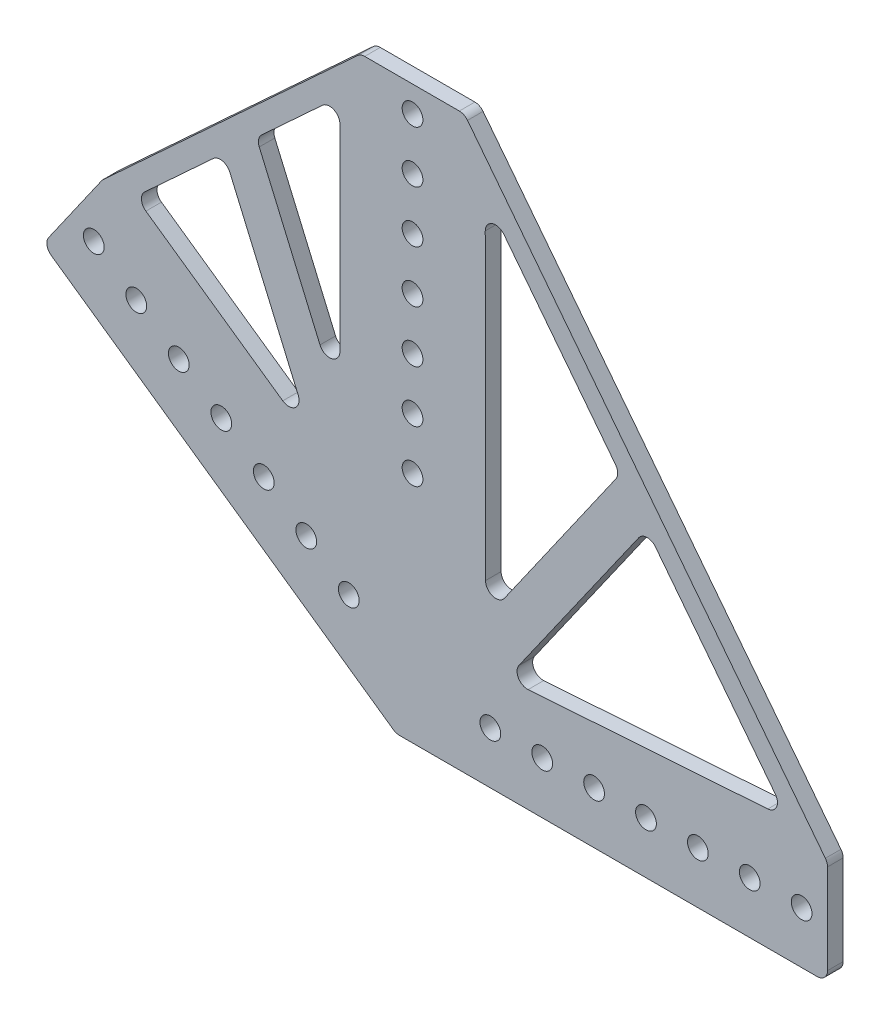
SolidWorks part; units mm, degrees
ref_plane "Front Plane" through (0, 0, 0) normal (0, 0, 1) x (1, 0, 0)
ref_plane "Top Plane" through (0, 0, 0) normal (0, 1, 0) x (1, 0, 0)
ref_plane "Right Plane" through (0, 0, 0) normal (1, 0, 0) x (0, 0, -1)
sketch "Sketch1" plane through (0, 0, 0) normal (0, 0, 1) x (1, 0, 0)
  line L0 (-280.0652, 184.4073) -> (-30.3877, 9.5812)
  line L1 (0, 0) -> (431.8, 0)
  line L2 (0, 0) -> (0, 25.4)
  line L3 (0, 25.4) -> (431.8, 25.4)
  line L4 (431.8, 0) -> (431.8, 25.4)
  line L5 (-280.0652, 184.4073) -> (-265.4964, 205.2137)
  line L6 (-30.3877, 9.5812) -> (-15.8188, 30.3877)
  line L7 (-265.4964, 205.2137) -> (-15.8188, 30.3877)
  line L8 (-25.4, 50.8) -> (0, 50.8)
  line L9 (-25.4, 50.8) -> (-25.4, 355.6)
  line L10 (0, 50.8) -> (0, 355.6)
  line L11 (-25.4, 355.6) -> (0, 355.6)
  line L12 (-225.8432, 161.9445) -> (23.8343, -12.8816) construction
  line L13 (0, 12.7) -> (431.8, 12.7) construction
  line L14 (-12.7, 12.7) -> (-12.7, 105.3379) construction
  line L15 (-12.7, 57.15) -> (-12.7, 69.85) construction
  line L16 (6.35, 12.7) -> (19.05, 12.7) construction
  line L17 (-28.3048, 23.6266) -> (-38.7081, 30.9111) construction
  line L18 (-103.2103, 60.5721) -> (-88.6414, 81.3786)
  line L20 (-25.4, 139.7) -> (0, 139.7)
  line L22 (88.9, 25.4) -> (88.9, 0)
  line L23 (88.9, 0) -> (-16.7043, 0)
  line L24 (-16.7043, 0) -> (-103.2103, 60.5721)
  line L25 (-88.6414, 81.3786) -> (-15.8188, 30.3877) construction
  line L26 (0, 25.4) -> (88.9, 25.4) construction
  line L27 (-25.4, 139.7) -> (-25.4, 50.8) construction
  line L28 (0, 139.7) -> (0, 50.8) construction
  line L29 (0, 0) -> (88.9, 0) construction
  line L30 (-88.6414, 81.3786) -> (-25.4, 139.7)
  line L31 (0, 139.7) -> (88.9, 25.4)
  circle A0 centre (-12.7, 57.15) radius 2.54
  circle A1 centre (-12.7, 69.85) radius 2.54
  circle A2 centre (-12.7, 82.55) radius 2.54
  circle A3 centre (-12.7, 95.25) radius 2.54
  circle A4 centre (-12.7, 107.95) radius 2.54
  circle A5 centre (-12.7, 120.65) radius 2.54
  circle A6 centre (-12.7, 133.35) radius 2.54
  circle A7 centre (-12.7, 146.05) radius 2.54
  circle A8 centre (-12.7, 158.75) radius 2.54
  circle A9 centre (-12.7, 171.45) radius 2.54
  circle A10 centre (-12.7, 184.15) radius 2.54
  circle A11 centre (-12.7, 196.85) radius 2.54
  circle A12 centre (-12.7, 209.55) radius 2.54
  circle A13 centre (-12.7, 222.25) radius 2.54
  circle A14 centre (-12.7, 234.95) radius 2.54
  circle A15 centre (-12.7, 247.65) radius 2.54
  circle A16 centre (-12.7, 260.35) radius 2.54
  circle A17 centre (-12.7, 273.05) radius 2.54
  circle A18 centre (-12.7, 285.75) radius 2.54
  circle A19 centre (-12.7, 298.45) radius 2.54
  circle A20 centre (-12.7, 311.15) radius 2.54
  circle A21 centre (-12.7, 323.85) radius 2.54
  circle A22 centre (-12.7, 336.55) radius 2.54
  circle A23 centre (-12.7, 349.25) radius 2.54
  circle A24 centre (6.35, 12.7) radius 2.54
  circle A25 centre (19.05, 12.7) radius 2.54
  circle A26 centre (31.75, 12.7) radius 2.54
  circle A27 centre (44.45, 12.7) radius 2.54
  circle A28 centre (57.15, 12.7) radius 2.54
  circle A29 centre (69.85, 12.7) radius 2.54
  circle A30 centre (82.55, 12.7) radius 2.54
  circle A31 centre (95.25, 12.7) radius 2.54
  circle A32 centre (107.95, 12.7) radius 2.54
  circle A33 centre (120.65, 12.7) radius 2.54
  circle A34 centre (133.35, 12.7) radius 2.54
  circle A35 centre (146.05, 12.7) radius 2.54
  circle A36 centre (158.75, 12.7) radius 2.54
  circle A37 centre (171.45, 12.7) radius 2.54
  circle A38 centre (184.15, 12.7) radius 2.54
  circle A39 centre (196.85, 12.7) radius 2.54
  circle A40 centre (209.55, 12.7) radius 2.54
  circle A41 centre (222.25, 12.7) radius 2.54
  circle A42 centre (234.95, 12.7) radius 2.54
  circle A43 centre (247.65, 12.7) radius 2.54
  circle A44 centre (260.35, 12.7) radius 2.54
  circle A45 centre (273.05, 12.7) radius 2.54
  circle A46 centre (285.75, 12.7) radius 2.54
  circle A47 centre (298.45, 12.7) radius 2.54
  circle A48 centre (311.15, 12.7) radius 2.54
  circle A49 centre (323.85, 12.7) radius 2.54
  circle A50 centre (336.55, 12.7) radius 2.54
  circle A51 centre (349.25, 12.7) radius 2.54
  circle A52 centre (361.95, 12.7) radius 2.54
  circle A53 centre (374.65, 12.7) radius 2.54
  circle A54 centre (387.35, 12.7) radius 2.54
  circle A55 centre (400.05, 12.7) radius 2.54
  circle A56 centre (412.75, 12.7) radius 2.54
  circle A57 centre (425.45, 12.7) radius 2.54
  circle A58 centre (-28.3048, 23.6266) radius 2.54
  circle A59 centre (-38.7081, 30.9111) radius 2.54
  circle A60 centre (-49.1113, 38.1955) radius 2.54
  circle A61 centre (-59.5145, 45.4799) radius 2.54
  circle A62 centre (-69.9178, 52.7643) radius 2.54
  circle A63 centre (-80.321, 60.0487) radius 2.54
  circle A64 centre (-90.7242, 67.3332) radius 2.54
  circle A65 centre (-101.1275, 74.6176) radius 2.54
  circle A66 centre (-111.5307, 81.902) radius 2.54
  circle A67 centre (-121.9339, 89.1864) radius 2.54
  circle A68 centre (-132.3372, 96.4708) radius 2.54
  circle A69 centre (-142.7404, 103.7553) radius 2.54
  circle A70 centre (-153.1436, 111.0397) radius 2.54
  circle A71 centre (-163.5468, 118.3241) radius 2.54
  circle A72 centre (-173.9501, 125.6085) radius 2.54
  circle A73 centre (-184.3533, 132.8929) radius 2.54
  circle A74 centre (-194.7565, 140.1774) radius 2.54
  circle A75 centre (-205.1598, 147.4618) radius 2.54
  circle A76 centre (-215.563, 154.7462) radius 2.54
  circle A77 centre (-225.9662, 162.0306) radius 2.54
  circle A78 centre (-236.3695, 169.315) radius 2.54
  circle A79 centre (-246.7727, 176.5995) radius 2.54
  circle A80 centre (-257.1759, 183.8839) radius 2.54
  circle A81 centre (-267.5792, 191.1683) radius 2.54
  circle A82 centre (-80.321, 60.0487) radius 2.54
  circle A83 centre (-69.9178, 52.7643) radius 2.54
  circle A84 centre (-59.5145, 45.4799) radius 2.54
  circle A85 centre (-49.1113, 38.1955) radius 2.54
  circle A86 centre (-38.7081, 30.9111) radius 2.54
  circle A87 centre (-28.3048, 23.6266) radius 2.54
  circle A88 centre (82.55, 12.7) radius 2.54
  circle A89 centre (-12.7, 133.35) radius 2.54
  circle A90 centre (-90.7242, 67.3332) radius 2.54
  circle A91 centre (69.85, 12.7) radius 2.54
  circle A92 centre (57.15, 12.7) radius 2.54
  circle A93 centre (44.45, 12.7) radius 2.54
  circle A94 centre (31.75, 12.7) radius 2.54
  circle A95 centre (19.05, 12.7) radius 2.54
  circle A96 centre (6.35, 12.7) radius 2.54
  circle A97 centre (-12.7, 120.65) radius 2.54
  circle A98 centre (-12.7, 107.95) radius 2.54
  circle A99 centre (-12.7, 95.25) radius 2.54
  circle A100 centre (-12.7, 82.55) radius 2.54
  circle A101 centre (-12.7, 69.85) radius 2.54
  circle A102 centre (-12.7, 57.15) radius 2.54
  circle A103 centre (-80.321, 60.0487) radius 2.54
  circle A104 centre (-69.9178, 52.7643) radius 2.54
  circle A105 centre (-59.5145, 45.4799) radius 2.54
  circle A106 centre (-49.1113, 38.1955) radius 2.54
  circle A107 centre (-38.7081, 30.9111) radius 2.54
  circle A108 centre (-28.3048, 23.6266) radius 2.54
  point P12 (-23.1032, 19.9844)
  point P17 (0, 12.7)
  point P19 (-12.7, 12.7)
  point P22 (-12.7, 50.8)
  point P214 (-95.9258, 70.9754)
  dimension "D12" = 5.08
  dimension "D15" = 5.08
  dimension "D19" = 5.08
  dimension "D20" = 6.35
  dimension "D1" = 25.4
  dimension "D2" = 431.8
  dimension "D3" = 25.4
  dimension "D4" = 25.4
  dimension "D5" = 304.8
  dimension "D6" = 304.8
  dimension "D7" = 145
  dimension "D8" = 12.7
  dimension "D9" = 12.7
  dimension "D10" = 38.1
  dimension "D11" = 6.35
  dimension "D14" = 12.7
  dimension "D16" = 6.35
  dimension "D18" = 12.7
  dimension "D21" = 12.7
  dimension "D24" = 6.35
  dimension "D25" = 6.35
  dimension "D26" = 6.35
  dimension "D13" = 24
  dimension "D17" = 34
  dimension "D22" = 24
  dimension "D23" = 7
  dimension "D27" = 7
  dimension "D28" = 7
  dimension "D29" = 7
extrude "Boss-Extrude3" add sketch "Sketch1" along normal blind 3.81 contours L22 L23 L24 L18 L30 L20 L31
extrude "Cut-Extrude6" cut sketch "Sketch1<7>" along normal blind 3.81 contours A64 | A63 | A62 | A61 | A60 | A59 | A58 | A24 | A25 | A26 | A27 | A28 | A29 | A30 | A0 | A1 | A2 | A3 | A4 | A5 | A6
sketch "Sketch1<7>" plane through (0, 0, 0) normal (0, 0, 1) x (1, 0, 0) same geometry as "Sketch1"
sketch "Sketch2" plane through (0, 0, 3.81) normal (0, 0, 1) x (1, 0, 0)
  line L0 (-25.4, 139.7) -> (-25.4, 6.0888) construction
  line L1 (-16.7043, 0) -> (-103.2103, 60.5721) construction
  line L2 (0, 139.7) -> (0, 0) construction
  line L3 (-103.2103, 60.5721) -> (-16.7043, 0) construction
  line L4 (-88.6414, 81.3786) -> (27.5793, 0) construction
  line L5 (88.9, 0) -> (-16.7043, 0) construction
  line L6 (44.45, 82.55) -> (-13.3521, 0)
  line L7 (0, 139.7) -> (88.9, 25.4) construction
  line L8 (-57.0207, 110.5393) -> (44.9189, 0) construction
  line L9 (-88.6414, 81.3786) -> (-25.4, 139.7) construction
  line L13 (-37.1403, 51.5186) -> (-80.5597, 81.9212)
  line L14 (-80.5597, 81.9212) -> (-58.85, 101.9419)
  line L15 (-58.85, 101.9419) -> (-37.1403, 51.5186)
  line L19 (-50.9321, 109.2438) -> (-30.48, 128.1048)
  line L20 (-30.48, 128.1048) -> (-30.48, 61.7414)
  line L21 (-30.48, 61.7414) -> (-50.9321, 109.2438)
  line L25 (38.1375, 82.3916) -> (5.094, 124.8761)
  line L26 (5.094, 124.8761) -> (5.1787, 35.3214)
  line L27 (5.1787, 35.3214) -> (38.1375, 82.3916)
  line L31 (44.6566, 74.0099) -> (79.0298, 29.8159)
  line L32 (79.0298, 29.8159) -> (10.2835, 25.1074)
  line L33 (10.2835, 25.1074) -> (44.6566, 74.0099)
extrude "Cut-Extrude7" cut sketch "Sketch2" against normal through all contours L15 L14 L13 | L21 L20 L19 | L26 L27 L25 | L33 L32 L31 region at (-58.85, 78.4606, 3.81) region at (-37.2974, 99.6967, 3.81) region at (16.1367, 80.8631, 3.81) region at (44.6566, 42.9777, 3.81)
fillet "Fillet1" radius 2.54 12 edges at (10.2835, 25.1074, 1.905) (44.6566, 74.0099, 1.905) (79.0298, 29.8159, 1.905) (5.1787, 35.3214, 1.905) (38.1375, 82.3916, 1.905) (5.094, 124.8761, 1.905) (-50.9321, 109.2438, 1.905) (-30.48, 128.1048, 1.905) (-30.48, 61.7414, 1.905) (-37.1403, 51.5186, 1.905) (-80.5597, 81.9212, 1.905) (-58.85, 101.9419, 1.905)
fillet "Fillet2" radius 2.54 7 edges at (-103.2103, 60.5721, 1.905) (-88.6414, 81.3786, 1.905) (-25.4, 139.7, 1.905) (0, 139.7, 1.905) (88.9, 25.4, 1.905) (88.9, 0, 1.905) (-16.7043, 0, 1.905)
